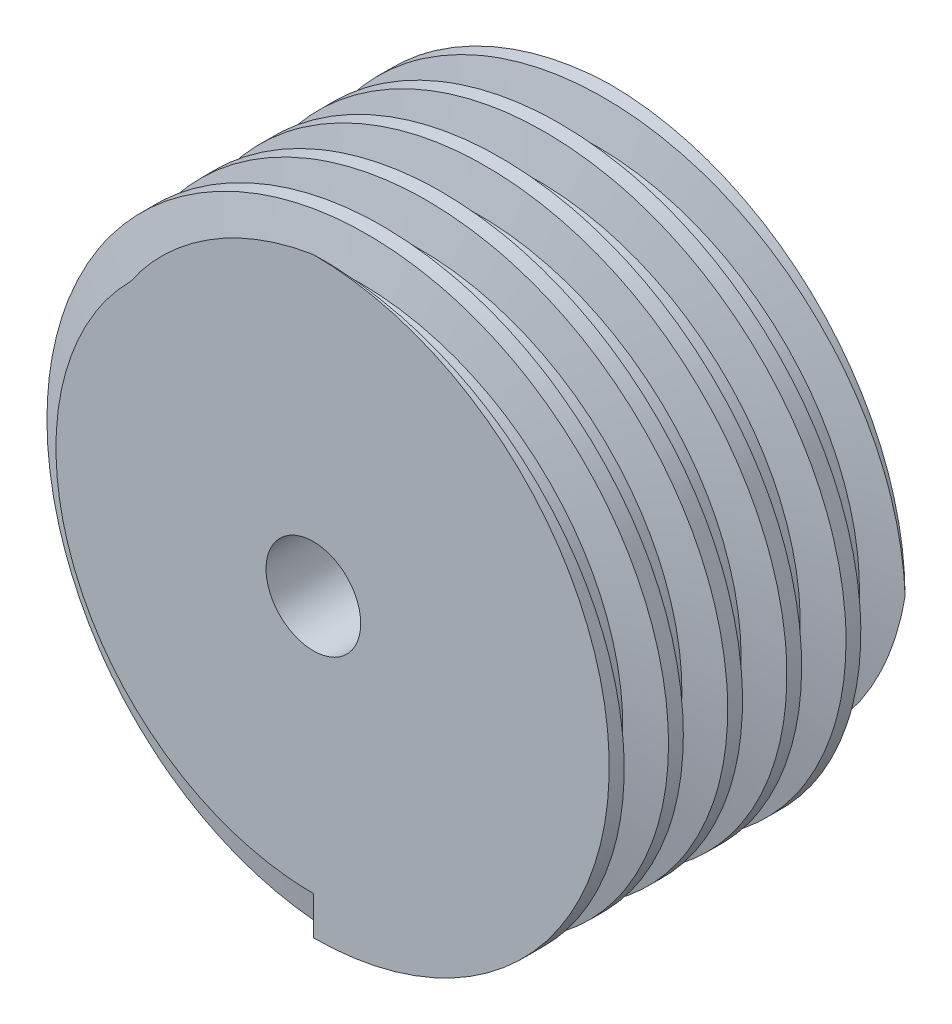
SolidWorks part; units mm, degrees
ref_plane "前基準面" through (0, 0, 0) normal (0, 0, 1) x (1, 0, 0)
ref_plane "上基準面" through (0, 0, 0) normal (0, 1, 0) x (1, 0, 0)
ref_plane "右基準面" through (0, 0, 0) normal (1, 0, 0) x (0, 0, -1)
sketch "草圖1" plane through (0, 0, 0) normal (0, 0, 1) x (1, 0, 0)
  circle A0 centre (0, 0) radius 10
  dimension "D1" = 20
extrude "填料-伸長1" add sketch "草圖1" along normal blind 10
sketch "草圖6" plane through (0, 0, 0) normal (0, 0, 1) x (1, 0, 0)
  circle A0 centre (0, 0) radius 9.9926
curve "螺旋曲線/渦捲線2" pitch 2 height 11 radius 9.9926 centre (0, 0, 0) axis (0, 0, 1) start towards (0, 1, 0)
sketch "草圖10" plane through (0, 0, 0) normal (1, 0, 0) x (0, 0, -1)
  line L1 (0.75, 10.0026) -> (0.75, 8.7026) construction
  line L5 (0.25, 8.7026) -> (1.25, 8.7026)
  line L6 (0, 10.0026) -> (0.25, 8.7026)
  line L10 (0, 11.2781) -> (0, -11.2781) construction
  line L13 (0.5, 3) -> (0.5, 2.3109) construction
  line L17 (0, 10.0026) -> (1.5, 10.0026)
  line L19 (1.25, 8.7026) -> (1.5, 10.0026)
  dimension "D1" = 1.5
  dimension "D2" = 0.5
  dimension "D3" = 1
  dimension "D4" = 1.3
sweep "除料-掃出3" cut profiles "草圖10" path "螺旋曲線/渦捲線2" align with end faces yes
ref_plane "平面1" through (0, 0, 10) normal (0, 0, 1) x (1, 0, 0)
sketch "草圖12" plane through (0, 0, 10) normal (0, 0, 1) x (1, 0, 0)
  circle A0 centre (0, 0) radius 1.6
  dimension "D1" = 3.2
extrude "除料-伸長2" cut sketch "草圖12" against normal blind 11.5 contours A0
